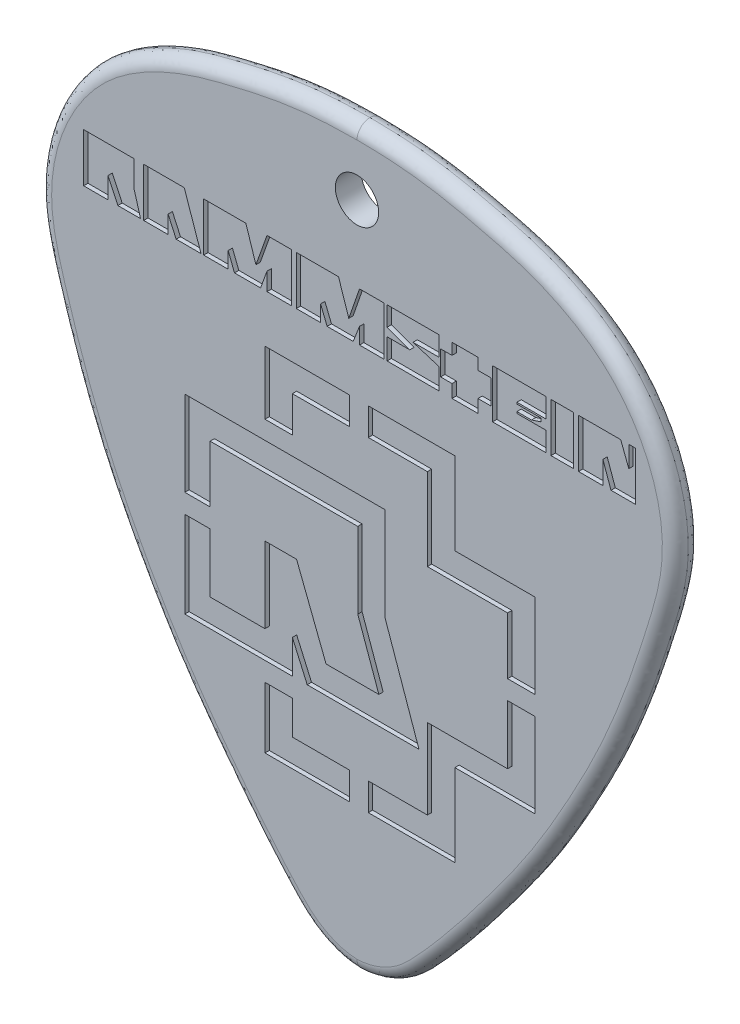
SolidWorks part; units mm, degrees
material "Nickel"
ref_plane "Front Plane" through (0, 0, 0) normal (0, 0, 1) x (1, 0, 0)
ref_plane "Top Plane" through (0, 0, 0) normal (0, 1, 0) x (1, 0, 0)
ref_plane "Right Plane" through (0, 0, 0) normal (1, 0, 0) x (0, 0, -1)
sketch "Sketch9" plane through (-49.9652, -1.9798, 0) normal (0, 0, 1) x (1, 0, 0)
  line L0 (49.9312, 18.5668) -> (49.9312, -17.1079) construction
  circle A1 centre (49.9312, 15.0287) radius 1
  spline S0 degree 3 poles (49.9312, 18.0287) (50.5822, 18.0238) (52.0435, 17.9887) (54.0305, 17.7033) (55.988, 17.2529) (58.0088, 16.7337) (60.0094, 15.8622) (62.6561, 14.0289) (64.4616, 11.0538) (64.7875, 7.3749) (63.9283, 4.4589) (62.9446, 1.4332) (61.7117, -1.5745) (60.1785, -4.5073) (58.5607, -7.295) (56.6435, -9.9646) (54.8628, -12.2747) (53.3893, -13.9945) (51.9899, -15.4429) (50.7935, -15.9421) (49.9312, -15.9653) knots 0 0 0 0 0.039894 0.08945 0.122624 0.162957 0.217169 0.255208 0.359361 0.416146 0.477175 0.543509 0.611614 0.675829 0.746189 0.80884 0.877031 0.924799 0.947638 1 1 1 1
  spline S1 degree 3 poles (49.9312, 18.0287) (49.2802, 18.0238) (47.819, 17.9887) (45.832, 17.7033) (43.8744, 17.2529) (41.8537, 16.7337) (39.853, 15.8622) (37.2063, 14.0289) (35.4008, 11.0538) (35.075, 7.3749) (35.9342, 4.4589) (36.9178, 1.4332) (38.1507, -1.5745) (39.684, -4.5073) (41.3018, -7.295) (43.219, -9.9646) (44.9997, -12.2747) (46.4731, -13.9945) (47.8725, -15.4429) (49.0689, -15.9421) (49.9312, -15.9653) knots 0 0 0 0 0.039894 0.08945 0.122624 0.162957 0.217169 0.255208 0.359361 0.416146 0.477175 0.543509 0.611614 0.675829 0.746189 0.80884 0.877031 0.924799 0.947638 1 1 1 1
  dimension "D1" = 2
  dimension "D2" = 3
extrude "mediator_2" add sketch "Sketch9" against normal blind 1.2 separate body
sketch "Sketch10" plane through (-49.9652, -1.9798, 0) normal (0, 0, 1) x (1, 0, 0)
  line L78 (101.711, 196.2021) -> (368.3776, 196.2021) construction
  line L79 (39.6213, 11.5287) -> (39.6213, 10.3368)
  line L80 (37.2943, 9.2785) -> (38.419, 9.2785)
  line L81 (37.2943, 9.2785) -> (37.2943, 11.5287)
  line L82 (37.2943, 11.5287) -> (39.6213, 11.5287)
  line L83 (62.7948, 9.2785) -> (62.7948, 11.5287)
  line L84 (39.6213, 10.3368) -> (39.9259, 9.2785)
  line L85 (38.419, 9.2785) -> (38.419, 10.2495)
  line L86 (38.419, 10.2495) -> (38.8771, 9.2785)
  line L87 (38.8771, 9.2785) -> (39.9259, 9.2785)
  line L88 (40.0704, 9.2785) -> (40.0704, 11.5287)
  line L89 (40.0704, 11.5287) -> (41.9447, 11.5287)
  line L90 (40.0704, 9.2785) -> (41.1994, 9.2785)
  line L91 (41.1994, 9.2785) -> (41.1994, 10.0986)
  line L92 (41.1994, 10.0986) -> (41.5727, 9.2785)
  line L93 (41.5727, 9.2785) -> (42.7203, 9.2785)
  line L94 (41.9447, 11.5287) -> (42.7203, 9.2785)
  line L95 (42.8452, 11.5287) -> (42.8452, 9.2785)
  line L96 (42.8452, 9.2785) -> (43.9744, 9.2785)
  line L97 (42.8452, 11.5287) -> (44.794, 11.5287)
  line L98 (46.8969, 11.5287) -> (46.8969, 9.2785)
  line L99 (47.1236, 9.2785) -> (47.1236, 11.5287)
  line L100 (47.1236, 11.5287) -> (49.0768, 11.5287)
  line L101 (47.1236, 9.2785) -> (48.2472, 9.2785)
  line L102 (51.1763, 11.5287) -> (51.1763, 9.2785)
  line L103 (51.3206, 9.2785) -> (51.3206, 10.2495)
  line L104 (51.3206, 11.5287) -> (53.725, 11.5287)
  line L105 (51.3206, 9.2785) -> (53.725, 9.2785)
  line L106 (53.725, 11.5287) -> (53.725, 10.6277)
  line L107 (55.52, 11.0032) -> (55.52, 11.5287)
  line L108 (53.7944, 11.0032) -> (54.3202, 11.0032)
  line L109 (53.7944, 11.0032) -> (53.7944, 9.8774)
  line L110 (53.7944, 9.8774) -> (54.3202, 9.8774)
  line L111 (56.1212, 11.0032) -> (56.1212, 9.8774)
  line L112 (54.3202, 9.2785) -> (55.52, 9.2785)
  line L113 (54.3202, 9.2785) -> (54.3202, 9.8774)
  line L114 (54.3202, 11.5287) -> (55.52, 11.5287)
  line L115 (55.52, 9.2785) -> (55.52, 9.8774)
  line L116 (54.3202, 11.0032) -> (54.3202, 11.5287)
  line L117 (55.52, 11.0032) -> (56.1212, 11.0032)
  line L118 (55.52, 9.8774) -> (56.1212, 9.8774)
  line L119 (54.3202, 11.5287) -> (55.52, 11.5287)
  line L120 (54.3202, 9.2785) -> (55.52, 9.2785)
  line L121 (43.9744, 9.2785) -> (43.9744, 10.0267)
  line L122 (43.9744, 10.0267) -> (44.2682, 9.2785)
  line L123 (45.7696, 9.2785) -> (45.7696, 10.0986)
  line L124 (45.7696, 10.0986) -> (45.4724, 9.2785)
  line L125 (44.2682, 9.2785) -> (45.4724, 9.2785)
  line L126 (45.7696, 9.2785) -> (46.8969, 9.2785)
  line L127 (44.794, 11.5287) -> (45.2581, 10.0986)
  line L128 (45.2581, 10.0986) -> (45.7696, 11.5287)
  line L129 (45.7696, 11.5287) -> (46.8969, 11.5287)
  line L130 (49.0768, 11.5287) -> (49.5501, 10.0986)
  line L131 (49.5501, 10.0986) -> (50.0466, 11.5287)
  line L132 (50.0466, 11.5287) -> (51.1763, 11.5287)
  line L133 (48.2472, 9.2785) -> (48.2472, 10.0267)
  line L134 (48.2472, 10.0267) -> (48.55, 9.2785)
  line L135 (48.55, 9.2785) -> (49.7528, 9.2785)
  line L136 (50.0466, 9.2785) -> (50.0466, 10.0267)
  line L137 (50.0466, 10.0267) -> (49.7528, 9.2785)
  line L138 (50.0466, 9.2785) -> (51.1763, 9.2785)
  line L139 (51.3206, 10.2495) -> (52.3702, 10.2495)
  line L140 (52.3702, 10.2495) -> (51.3206, 10.6277)
  line L141 (51.3206, 10.6277) -> (51.3206, 11.5287)
  line L142 (53.725, 10.6277) -> (52.5197, 10.6277)
  line L143 (52.5197, 10.6277) -> (53.725, 10.2534)
  line L144 (53.725, 10.2534) -> (53.725, 9.2785)
  line L145 (56.1952, 11.5287) -> (56.1952, 9.2785)
  line L146 (56.1952, 11.5287) -> (58.6695, 11.5287)
  line L147 (56.1952, 9.2785) -> (58.6695, 9.2785)
  line L148 (58.6695, 11.5287) -> (58.6695, 10.6277)
  line L149 (58.6695, 10.6277) -> (57.3202, 10.6277)
  line L150 (57.3202, 10.6277) -> (57.3202, 10.5531)
  line L151 (57.3202, 10.5531) -> (58.4448, 10.5531)
  line L152 (58.4448, 10.5531) -> (58.4448, 10.4036)
  line L153 (58.4448, 10.4036) -> (57.9949, 10.2534)
  line L154 (57.9949, 10.2534) -> (57.3189, 10.2534)
  line L155 (57.3189, 10.2534) -> (57.3189, 10.1783)
  line L156 (57.3189, 10.1783) -> (58.6695, 10.1783)
  line L157 (58.6695, 10.1783) -> (58.6695, 9.2785)
  line L158 (58.8938, 11.5287) -> (58.8938, 9.2785)
  line L159 (59.9445, 11.5287) -> (59.9445, 9.2785)
  line L160 (58.8938, 9.2785) -> (59.9445, 9.2785)
  line L161 (58.8938, 11.5287) -> (59.9445, 11.5287)
  line L162 (60.1688, 11.5287) -> (60.1688, 9.2785)
  line L163 (60.1688, 9.2785) -> (61.2951, 9.2785)
  line L164 (60.1688, 11.5287) -> (62.119, 11.5287)
  line L165 (62.4942, 11.5287) -> (62.4942, 10.5531)
  line L166 (62.4942, 10.5531) -> (62.119, 11.5287)
  line L167 (62.4942, 11.5287) -> (62.7948, 11.5287)
  line L168 (61.2951, 9.2785) -> (61.2951, 10.3281)
  line L169 (61.2951, 10.3281) -> (61.6698, 9.2785)
  line L170 (61.6698, 9.2785) -> (62.7948, 9.2785)
  circle A0 centre (49.9312, 15.0287) radius 1 construction
  dimension "D1" = 3.5
fillet "Fillet3" radius 0.6 4 edges
extrude "Rammstein" cut sketch "Sketch10" against normal blind 0.2 contours L86 L87 L84 L79 L82 L81 L80 L85 | L94 L89 L88 L90 L91 L92 L93 | L129 L128 L127 L97 L95 L96 L121 L122 L125 L124 L123 L126 L98 | L136 L138 L102 L132 L131 L130 L100 L99 L101 L133 L134 L135 L137 | L144 L143 L142 L106 L104 L141 L140 L139 L103 L105 | L115 L118 L111 L117 L107 L114 L116 L108 L109 L110 L113 L112 | L157 L156 L155 L154 L153 L152 L151 L150 L149 L148 L146 L145 L147 | L169 L170 L83 L167 L165 L166 L164 L162 L163 L168 | L158 L160 L159 L161 region at (-11.4729, 8.4341, 0) region at (11.4894, 8.4248, 0) region at (-8.7561, 8.3839, 0) region at (-5.1297, 8.3929, 0) region at (-0.8494, 8.3928, 0) region at (2.5553, 8.4204, 0) region at (4.9798, 8.4355, 0) region at (7.4256, 8.4244, 0)
sketch "Sketch11" plane through (0, 0, 0) normal (0, 0, 1) x (1, 0, 0)
  line L0 (25.7842, 90.0176) -> (159.1175, 90.0176) construction
  line L17 (-0.3902, 3.8019) -> (-3.0225, 3.8019)
  line L18 (-4.2901, 2.1447) -> (-3.0225, 2.1447)
  line L19 (-4.2901, 2.1447) -> (-4.2901, 5.0698)
  line L20 (-4.2901, 5.0698) -> (-0.3902, 5.0698)
  line L21 (-0.3902, 3.8019) -> (-0.3902, 5.0698)
  line L22 (-3.0225, 3.8019) -> (-3.0225, 2.1447)
  line L23 (0.4867, 3.8019) -> (3.2168, 3.8019)
  line L24 (8.19, -2.6327) -> (6.9237, -2.6327)
  line L25 (8.19, -2.6327) -> (8.19, 1.2674)
  line L26 (4.4865, 5.0698) -> (0.4867, 5.0698)
  line L27 (0.4867, 3.8019) -> (0.4867, 5.0698)
  line L28 (3.2168, 3.8019) -> (3.2168, 0)
  line L29 (3.2168, 0) -> (6.9237, 0)
  line L30 (6.9237, 0) -> (6.9237, -2.6327)
  line L31 (8.19, 1.2674) -> (4.4865, 1.2674)
  line L32 (4.4865, 1.2674) -> (4.4865, 5.0698)
  line L33 (8.19, -3.511) -> (8.19, -7.4102)
  line L34 (8.19, -7.4102) -> (4.4865, -7.4102)
  line L35 (4.4865, -7.4102) -> (4.4865, -11.2134)
  line L36 (4.4865, -11.2134) -> (0.4873, -11.2134)
  line L37 (0.4873, -11.2134) -> (0.4873, -9.945)
  line L38 (0.4873, -9.945) -> (3.2173, -9.945)
  line L39 (3.2173, -9.945) -> (3.2173, -6.2391)
  line L40 (3.2173, -6.2391) -> (6.9237, -6.2391)
  line L41 (6.9237, -6.2391) -> (6.9237, -3.511)
  line L42 (6.9237, -3.511) -> (8.19, -3.511)
  line L43 (-4.2901, -8.385) -> (-4.2901, -11.2134)
  line L44 (-4.2901, -11.2134) -> (-0.3902, -11.2134)
  line L45 (-0.3902, -11.2134) -> (-0.3902, -9.945)
  line L46 (-0.3902, -9.945) -> (-3.0225, -9.945)
  line L47 (-3.0225, -9.945) -> (-3.0225, -8.385)
  line L48 (-3.0225, -8.385) -> (-4.2901, -8.385)
  line L49 (-7.9951, -2.6327) -> (-6.8231, -2.6327)
  line L50 (-7.9951, 1.2989) -> (1.269, 1.2989)
  line L51 (-7.9951, 1.2989) -> (-7.9951, -2.6327)
  line L52 (-7.9951, -7.5074) -> (-3.0225, -7.5074)
  line L54 (-6.8231, -2.6327) -> (-6.8231, 0)
  line L55 (-6.8231, 0) -> (0, 0)
  line L56 (0, 0) -> (0, -3.511)
  line L57 (0, -3.511) -> (0.975, -6.2391)
  line L58 (-7.9951, -3.511) -> (-6.8231, -3.511)
  line L59 (-6.8231, -3.511) -> (-6.8231, -6.2391)
  line L60 (-6.8231, -6.2391) -> (-4.2901, -6.2391)
  line L61 (-4.2901, -6.2391) -> (-4.2901, -2.7299)
  line L62 (-4.2901, -2.7299) -> (-2.8275, -2.7299)
  line L63 (-2.8275, -2.7299) -> (-1.4654, -6.2391)
  line L64 (-1.4654, -6.2391) -> (0.975, -6.2391)
  line L65 (1.269, 1.2989) -> (1.269, -3.0527)
  line L66 (1.269, -3.0527) -> (2.8295, -7.5074)
  line L67 (-3.0225, -7.5074) -> (-3.0225, -5.9535)
  line L68 (-3.0225, -5.9535) -> (-2.3359, -7.5074)
  line L69 (-2.3359, -7.5074) -> (2.8295, -7.5074)
  line L70 (-7.9951, -3.511) -> (-7.9951, -7.5074)
  line L71 (0, 0) -> (0, 19.7504) construction
  line L72 (0, 0) -> (15.2231, 0) construction
  dimension "D1" = 1.9479
  dimension "D2" = 0.8769
  dimension "D3" = 0.8776
  dimension "D4" = 0.8783
extrude "Logo" cut sketch "Sketch11" against normal blind 0.2
